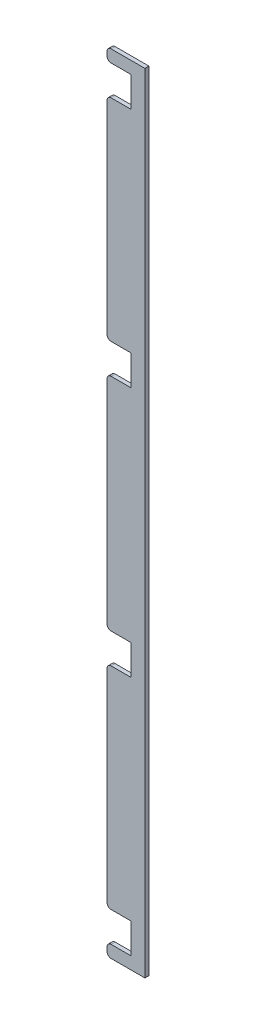
SolidWorks part; units mm, degrees
ref_plane "Front Plane" through (0, 0, 0) normal (0, 0, 1) x (1, 0, 0)
ref_plane "Top Plane" through (0, 0, 0) normal (0, 1, 0) x (1, 0, 0)
ref_plane "Right Plane" through (0, 0, 0) normal (1, 0, 0) x (0, 0, -1)
sketch "Sketch1" plane through (0, 0, 0) normal (0, 0, 1) x (1, 0, 0)
  line L0 (0, -182.5952) -> (-4.5, -182.5952)
  line L2 (0, 13.4048) -> (0, -182.5952)
  line L6 (-4.5, 10.3548) -> (-3.5, 10.3548)
  line L7 (-3.5, 10.3548) -> (-3.5, 2.8548)
  line L8 (0, 2.4048) -> (0, -6.5952) construction
  line L9 (-3.5, 2.8548) -> (-4.5, 2.8548)
  line L10 (-4.5, -49.6452) -> (-3.5, -49.6452)
  line L11 (-3.5, -49.6452) -> (-3.5, -57.1452)
  line L12 (-3.5, -57.1452) -> (-4.5, -57.1452)
  line L13 (-4.5, -112.0452) -> (-3.5, -112.0452)
  line L14 (-3.5, -112.0452) -> (-3.5, -119.5452)
  line L15 (-3.5, -119.5452) -> (-4.5, -119.5452)
  line L16 (-4.5, -172.0452) -> (-3.5, -172.0452)
  line L17 (-3.5, -172.0452) -> (-3.5, -179.5452)
  line L18 (-3.5, -179.5452) -> (-4.5, -179.5452)
  line L100 (-8.4, 10.3548) -> (-4.5, 10.3548)
  line L101 (-4.5, 10.3548) -> (-4.5, 2.8548)
  line L102 (-4.5, 2.8548) -> (-8.4, 2.8548)
  line L103 (-9.4, 1.8548) -> (-9.4, -48.6452)
  line L104 (-8.4, -49.6452) -> (-4.5, -49.6452)
  line L105 (-4.5, -49.6452) -> (-4.5, -57.1452)
  line L106 (-4.5, -57.1452) -> (-8.4, -57.1452)
  line L107 (-9.4, -58.1452) -> (-9.4, -111.0452)
  line L108 (-8.4, -112.0452) -> (-4.5, -112.0452)
  line L109 (-4.5, -112.0452) -> (-4.5, -119.5452)
  line L110 (-4.5, -119.5452) -> (-8.4, -119.5452)
  line L111 (-9.4, -120.5452) -> (-9.4, -171.0452)
  line L112 (-8.4, -172.0452) -> (-4.5, -172.0452)
  line L113 (-4.5, -172.0452) -> (-4.5, -179.5452)
  line L114 (-4.5, -179.5452) -> (-8.4, -179.5452)
  line L115 (-9.4, -180.5452) -> (-9.4, -181.5952)
  line L116 (-8.4, -182.5952) -> (-4.5, -182.5952)
  line L117 (-4.5, -182.5952) -> (-4.5, -191.5952)
  line L118 (-4.5, -191.5952) -> (78.5, -191.5952)
  line L119 (78.5, -191.5952) -> (78.5, -182.5952)
  line L120 (78.5, -182.5952) -> (82.4, -182.5952)
  line L121 (83.4, -181.5952) -> (83.4, -180.5452)
  line L122 (82.4, -179.5452) -> (78.5, -179.5452)
  line L123 (78.5, -179.5452) -> (78.5, -172.0452)
  line L124 (78.5, -172.0452) -> (82.4, -172.0452)
  line L125 (83.4, -171.0452) -> (83.4, -120.5452)
  line L126 (82.4, -119.5452) -> (78.5, -119.5452)
  line L127 (78.5, -119.5452) -> (78.5, -112.0452)
  line L128 (78.5, -112.0452) -> (82.4, -112.0452)
  line L129 (83.4, -111.0452) -> (83.4, -58.1452)
  line L130 (82.4, -57.1452) -> (78.5, -57.1452)
  line L131 (78.5, -57.1452) -> (78.5, -49.6452)
  line L132 (78.5, -49.6452) -> (82.4, -49.6452)
  line L133 (83.4, -48.6452) -> (83.4, 1.8548)
  line L134 (82.4, 2.8548) -> (78.5, 2.8548)
  line L135 (78.5, 2.8548) -> (78.5, 10.3548)
  line L136 (78.5, 10.3548) -> (82.4, 10.3548)
  line L137 (83.4, 11.3548) -> (83.4, 12.4048)
  line L138 (82.4, 13.4048) -> (78.5, 13.4048)
  line L139 (78.5, 13.4048) -> (78.5, 22.4048)
  line L140 (78.5, 22.4048) -> (-4.5, 22.4048)
  line L141 (-4.5, 22.4048) -> (-4.5, 13.4048)
  line L142 (-4.5, 13.4048) -> (-8.4, 13.4048)
  line L143 (-9.4, 12.4048) -> (-9.4, 11.3548)
  line L144 (-8.4, 10.3548) -> (-4.5, 10.3548)
  line L145 (-4.5, 10.3548) -> (-4.5, 2.8548)
  line L146 (-4.5, 2.8548) -> (-8.4, 2.8548)
  line L147 (-9.4, 1.8548) -> (-9.4, -48.6452)
  line L148 (-8.4, -49.6452) -> (-4.5, -49.6452)
  line L149 (-4.5, -49.6452) -> (-4.5, -57.1452)
  line L150 (-4.5, -57.1452) -> (-8.4, -57.1452)
  line L151 (-9.4, -58.1452) -> (-9.4, -111.0452)
  line L152 (-8.4, -112.0452) -> (-4.5, -112.0452)
  line L153 (-4.5, -112.0452) -> (-4.5, -119.5452)
  line L154 (-4.5, -119.5452) -> (-8.4, -119.5452)
  line L155 (-9.4, -120.5452) -> (-9.4, -171.0452)
  line L156 (-8.4, -172.0452) -> (-4.5, -172.0452)
  line L157 (-4.5, -172.0452) -> (-4.5, -179.5452)
  line L158 (-4.5, -179.5452) -> (-8.4, -179.5452)
  line L159 (-9.4, -180.5452) -> (-9.4, -181.5952)
  line L160 (-8.4, -182.5952) -> (-4.5, -182.5952)
  line L186 (0, 13.4048) -> (-8.4, 13.4048)
  line L187 (-9.4, 12.4048) -> (-9.4, 11.3548)
  arc A40 (-8.4, 2.8548) -> (-9.4, 1.8548) centre (-8.4, 1.8548) ccw
  arc A41 (-9.4, -48.6452) -> (-8.4, -49.6452) centre (-8.4, -48.6452) ccw
  arc A42 (-8.4, -57.1452) -> (-9.4, -58.1452) centre (-8.4, -58.1452) ccw
  arc A43 (-9.4, -111.0452) -> (-8.4, -112.0452) centre (-8.4, -111.0452) ccw
  arc A44 (-8.4, -119.5452) -> (-9.4, -120.5452) centre (-8.4, -120.5452) ccw
  arc A45 (-9.4, -171.0452) -> (-8.4, -172.0452) centre (-8.4, -171.0452) ccw
  arc A46 (-8.4, -179.5452) -> (-9.4, -180.5452) centre (-8.4, -180.5452) ccw
  arc A47 (-9.4, -181.5952) -> (-8.4, -182.5952) centre (-8.4, -181.5952) ccw
  arc A48 (82.4, -182.5952) -> (83.4, -181.5952) centre (82.4, -181.5952) ccw
  arc A49 (83.4, -180.5452) -> (82.4, -179.5452) centre (82.4, -180.5452) ccw
  arc A50 (82.4, -172.0452) -> (83.4, -171.0452) centre (82.4, -171.0452) ccw
  arc A51 (83.4, -120.5452) -> (82.4, -119.5452) centre (82.4, -120.5452) ccw
  arc A52 (82.4, -112.0452) -> (83.4, -111.0452) centre (82.4, -111.0452) ccw
  arc A53 (83.4, -58.1452) -> (82.4, -57.1452) centre (82.4, -58.1452) ccw
  arc A54 (82.4, -49.6452) -> (83.4, -48.6452) centre (82.4, -48.6452) ccw
  arc A55 (83.4, 1.8548) -> (82.4, 2.8548) centre (82.4, 1.8548) ccw
  arc A56 (82.4, 10.3548) -> (83.4, 11.3548) centre (82.4, 11.3548) ccw
  arc A57 (83.4, 12.4048) -> (82.4, 13.4048) centre (82.4, 12.4048) ccw
  arc A58 (-8.4, 13.4048) -> (-9.4, 12.4048) centre (-8.4, 12.4048) ccw
  arc A59 (-9.4, 11.3548) -> (-8.4, 10.3548) centre (-8.4, 11.3548) ccw
  arc A60 (-8.4, 2.8548) -> (-9.4, 1.8548) centre (-8.4, 1.8548) ccw
  arc A61 (-9.4, -48.6452) -> (-8.4, -49.6452) centre (-8.4, -48.6452) ccw
  arc A62 (-8.4, -57.1452) -> (-9.4, -58.1452) centre (-8.4, -58.1452) ccw
  arc A63 (-9.4, -111.0452) -> (-8.4, -112.0452) centre (-8.4, -111.0452) ccw
  arc A64 (-8.4, -119.5452) -> (-9.4, -120.5452) centre (-8.4, -120.5452) ccw
  arc A65 (-9.4, -171.0452) -> (-8.4, -172.0452) centre (-8.4, -171.0452) ccw
  arc A66 (-8.4, -179.5452) -> (-9.4, -180.5452) centre (-8.4, -180.5452) ccw
  arc A67 (-9.4, -181.5952) -> (-8.4, -182.5952) centre (-8.4, -181.5952) ccw
  arc A78 (-8.4, 13.4048) -> (-9.4, 12.4048) centre (-8.4, 12.4048) ccw
  arc A79 (-9.4, 11.3548) -> (-8.4, 10.3548) centre (-8.4, 11.3548) ccw
  dimension "D1" = 1
  dimension "D2" = 0
extrude "Boss-Extrude1" add sketch "Sketch1" along normal blind 1 contours L2 region at (-4.508, -84.5952, 0)
